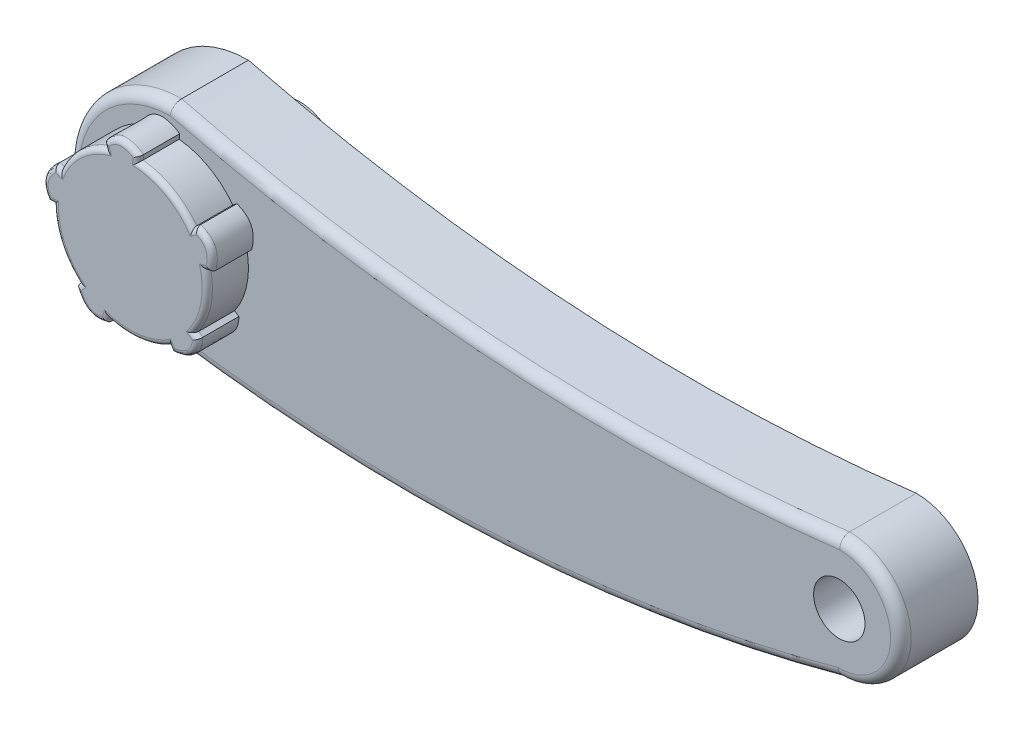
SolidWorks part; units mm, degrees
ref_plane "Front Plane" through (0, 0, 0) normal (0, 0, 1) x (1, 0, 0)
ref_plane "Top Plane" through (0, 0, 0) normal (0, 1, 0) x (1, 0, 0)
ref_plane "Right Plane" through (0, 0, 0) normal (1, 0, 0) x (0, 0, -1)
sketch "Sketch1" plane through (0, 0, 0) normal (0, 0, 1) x (1, 0, 0)
  line L0 (-65, 0) -> (65, 0)
  circle A0 centre (-65, 0) radius 20
  circle A1 centre (65, 0) radius 12
  arc A2 (-65, -20) -> (65, -12) centre (-19.0686, 293.8645) ccw
  arc A3 (-65, 20) -> (65, 12) centre (21.666, 368.0724) ccw
  point P4 (0, 0)
extrude "Boss-Extrude1" add sketch "Sketch1" along normal blind 15
fillet "Fillet1" radius 2 4 edges at (77, 0, 15) (0.415, -22.7441, 15) (-85, 0, 15) (-0.3661, 10.0501, 15)
sketch "Sketch3" plane through (0, 0, 15) normal (0, 0, 1) x (1, 0, 0)
  line L3 (-53.0459, 9.0682) -> (-52.2527, 9.6699)
  line L4 (-50.3335, 3.1665) -> (-49.3604, 3.3766)
  line L5 (-52.6816, -8.5668) -> (-51.8643, -9.1353)
  line L6 (-57.4563, -12.9701) -> (-56.9557, -13.8307)
  line L7 (-69.3409, -14.3627) -> (-69.629, -15.3158)
  line L8 (-75.0042, -11.1825) -> (-75.668, -11.9245)
  line L9 (-80.0012, -0.3099) -> (-80.9966, -0.3304)
  line L10 (-78.7267, 6.059) -> (-79.6375, 6.461)
  line L11 (-69.9303, 14.1712) -> (-70.2575, 15.1116)
  line L12 (-63.4794, 14.9271) -> (-63.3785, 15.9176)
  arc A0 (-53.0459, 9.0682) -> (-63.4794, 14.9271) centre (-65, 0) ccw
  arc A1 (-69.3409, -14.3627) -> (-57.4563, -12.9701) centre (-65, 0) ccw
  arc A2 (-52.6816, -8.5668) -> (-50.3335, 3.1665) centre (-65, 0) ccw
  arc A3 (-69.9303, 14.1712) -> (-78.7267, 6.059) centre (-65, 0) ccw
  arc A4 (-80.0012, -0.3099) -> (-75.0042, -11.1825) centre (-65, 0) ccw
  spline S0 degree 2 poles (-52.2527, 9.6699) (-48.076, 8.2033) (-49.3604, 3.3766) knots 0 0 0 1 1 1
  spline S1 degree 2 poles (-51.8643, -9.1353) (-51.9684, -13.5607) (-56.9557, -13.8307) knots 0 0 0 1 1 1
  spline S2 degree 2 poles (-69.629, -15.3158) (-73.87, -16.5843) (-75.668, -11.9245) knots 0 0 0 1 1 1
  spline S3 degree 2 poles (-80.9966, -0.3304) (-83.5136, 3.3111) (-79.6375, 6.461) knots 0 0 0 1 1 1
  spline S4 degree 2 poles (-70.2575, 15.1116) (-67.572, 18.6306) (-63.3785, 15.9176) knots 0 0 0 1 1 1
  point P22 (-65, 0)
  dimension "D1" = 25
  dimension "D2" = 5
extrude "Boss-Extrude2" add sketch "Sketch3" along normal blind 8
fillet "Fillet2" radius 1 20 edges at (-80.4989, -0.3201, 23) (-79.1821, 6.26, 23) (-75.1722, 11.0299, 23) (-70.0939, 14.6414, 23) (-63.4289, 15.4224, 23) (-57.6533, 13.0827, 23) (-52.6493, 9.369, 23) (-49.8469, 3.2716, 23) (-50.2873, -2.9443, 23) (-52.273, -8.851, 23) (-57.206, -13.4004, 23) (-63.2538, -14.9024, 23) (-69.485, -14.8393, 23) (-75.3361, -11.5535, 23) (-78.6335, -6.2659, 23)
sketch "Sketch5" plane through (0, 0, 15) normal (0, 0, 1) x (1, 0, 0)
  circle A0 centre (65, 0) radius 5
extrude "Cut-Extrude1" cut sketch "Sketch5" against normal blind 10
sketch "Sketch6" plane through (0, 0, 0) normal (0, 0, -1) x (-1, 0, 0)
  circle A0 centre (65, 0) radius 8
extrude "Boss-Extrude3" add sketch "Sketch6" along normal blind 10
